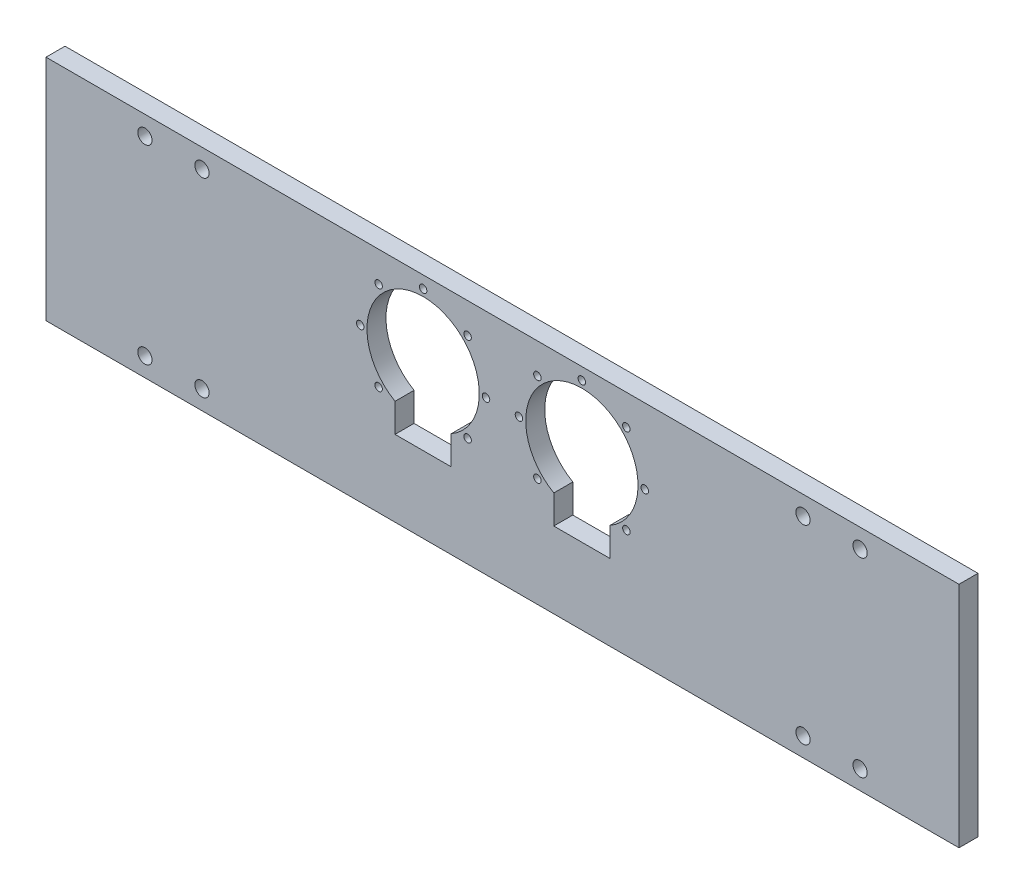
SolidWorks part; units mm, degrees
ref_plane "Front Plane" through (0, 0, 0) normal (0, 0, 1) x (1, 0, 0)
ref_plane "Top Plane" through (0, 0, 0) normal (0, 1, 0) x (1, 0, 0)
ref_plane "Right Plane" through (0, 0, 0) normal (1, 0, 0) x (0, 0, -1)
sketch "Sketch1" plane through (0, 0, 0) normal (0, 0, 1) x (1, 0, 0)
  line L0 (-304.8, 0) -> (304.8, 0) construction
  line L1 (-304.8, 76.2) -> (304.8, 76.2)
  line L2 (-304.8, 76.2) -> (-304.8, -76.2)
  line L3 (-304.8, -76.2) -> (304.8, -76.2)
  line L4 (304.8, 76.2) -> (304.8, -76.2)
  line L5 (-304.8, 76.2) -> (304.8, -76.2) construction
  line L6 (-304.8, -76.2) -> (304.8, 76.2) construction
  line L7 (0, 76.2) -> (0, -76.2) construction
  line L8 (53, 26.2) -> (53, -11.3) construction
  line L9 (53, 26.2) -> (34.25, -6.276) construction
  line L10 (53, 26.2) -> (71.75, -6.276) construction
  line L11 (34.25, -6.276) -> (34.25, -25.4)
  line L12 (71.75, -6.276) -> (71.75, -25.4)
  line L13 (71.75, -25.4) -> (34.25, -25.4)
  line L14 (238.76, 76.2) -> (238.76, -76.2) construction
  line L15 (200.66, 76.2) -> (200.66, -76.2) construction
  line L16 (-34.25, -6.276) -> (-34.25, -25.4)
  line L17 (-71.75, -25.4) -> (-34.25, -25.4)
  line L18 (-71.75, -6.276) -> (-71.75, -25.4)
  circle A5 centre (53, 26.2) radius 48 construction
  arc A6 (71.75, -6.276) -> (34.25, -6.276) centre (53, 26.2) ccw
  circle A7 centre (53, 26.2) radius 42 construction
  circle A8 centre (53, 68.2) radius 2.5
  circle A9 centre (82.6985, 55.8985) radius 2.5
  circle A10 centre (95, 26.2) radius 2.5
  circle A11 centre (82.6985, -3.4985) radius 2.5
  circle A13 centre (23.3015, -3.4985) radius 2.5
  circle A14 centre (11, 26.2) radius 2.5
  circle A15 centre (23.3015, 55.8985) radius 2.5
  arc A16 (55.4993, -15.7405) -> (50.5007, -15.7405) centre (53, -15.8) ccw [skipped]
  circle A17 centre (238.76, 63.5) radius 4.7625
  circle A18 centre (200.66, 63.5) radius 4.7625
  circle A19 centre (238.76, -63.5) radius 4.7625
  circle A20 centre (200.66, -63.5) radius 4.7625
  circle A21 centre (-82.6985, -3.4985) radius 2.5
  circle A22 centre (-95, 26.2) radius 2.5
  circle A23 centre (-82.6985, 55.8985) radius 2.5
  circle A24 centre (-53, 68.2) radius 2.5
  circle A25 centre (-23.3015, 55.8985) radius 2.5
  circle A26 centre (-11, 26.2) radius 2.5
  circle A27 centre (-23.3015, -3.4985) radius 2.5
  arc A28 (-71.75, -6.276) -> (-34.25, -6.276) centre (-53, 26.2) cw
  circle A29 centre (-238.76, 63.5) radius 4.7625
  circle A30 centre (-200.66, 63.5) radius 4.7625
  circle A31 centre (-200.66, -63.5) radius 4.7625
  circle A32 centre (-238.76, -63.5) radius 4.7625
  point P0 (0, 0)
  point P32 (53, 26.2)
  dimension "D3" = 96
  dimension "D6" = 75
  dimension "D7" = 84
  dimension "D8" = 5
  dimension "D15" = 9.525
  dimension "D17" = 9.525
  dimension "D1" = 609.6
  dimension "D2" = 152.4
  dimension "D4" = 53
  dimension "D5" = 50
  dimension "D10" = 30
  dimension "D11" = 30
  dimension "D12" = 50.8
  dimension "D13" = 66.04
  dimension "D14" = 38.1
  dimension "D16" = 12.7
  dimension "D18" = 12.7
  dimension "D9" = 8
extrude "Boss-Extrude1" add sketch "Sketch1" along normal blind 12.7
equation "\"bplate_length\"= 24in"
equation "\"bplate_height\"= 6in"
equation "\"bplate_thickness\"= 0.5in"
equation "\"motor_diameter\"= 96 / 25.4in"
equation "\"motor_clearance\"= 5 / 25.4in"
equation "\"motor_mount_hole_pattern_dia\"= 84 / 25.4in"
equation "\"motor_mount_hole_dia\"= 5 / 25.4in"
equation "\"motor_cx\"= \"motor_clearance\" + \"motor_diameter\" / 2in"
equation "\"motor_cy_top\"= \"motor_mount_hole_pattern_dia\" / 2 + \"motor_mount_hole_dia\" * 2in"
equation "\"D1@Sketch1\"=\"bplate_length\""
equation "\"D2@Sketch1\"=\"bplate_height\""
equation "\"motor_driver_cover_dia\"= 75 / 25.4in"
equation "\"D4@Sketch1\"=\"motor_cx\""
equation "\"motor_driver_cutout_clearance\"= 60deg"
equation "\"wire_cutout_clearance\"= 2in"
equation "\"connector_plate_thickness\"= 1in"
equation "\"connector_plate_hole_diameter\"= 0.375in"
equation "\"connector_plate_hole_depth\"= 1in"
equation "\"coonector_first_hole_offset\"= 1.6in"
equation "\"D14@Sketch1\"=1.5"
equation "\"D13@Sketch1\"=\"coonector_first_hole_offset\"+1in"
equation "\"D12@Sketch1\"=\"wire_cutout_clearance\""
equation "\"D16@Sketch1\"=\"connector_plate_thickness\"/2"
equation "\"D18@Sketch1\"=\"connector_plate_thickness\"/2"
equation "\"D15@Sketch1\"=\"connector_plate_hole_diameter\""
equation "\"D17@Sketch1\"=\"connector_plate_hole_diameter\""
equation "\"D8@Sketch1\"=\"motor_mount_hole_dia\""
equation "\"D6@Sketch1\"=\"motor_driver_cover_dia\""
equation "\"D7@Sketch1\"=\"motor_mount_hole_pattern_dia\""
